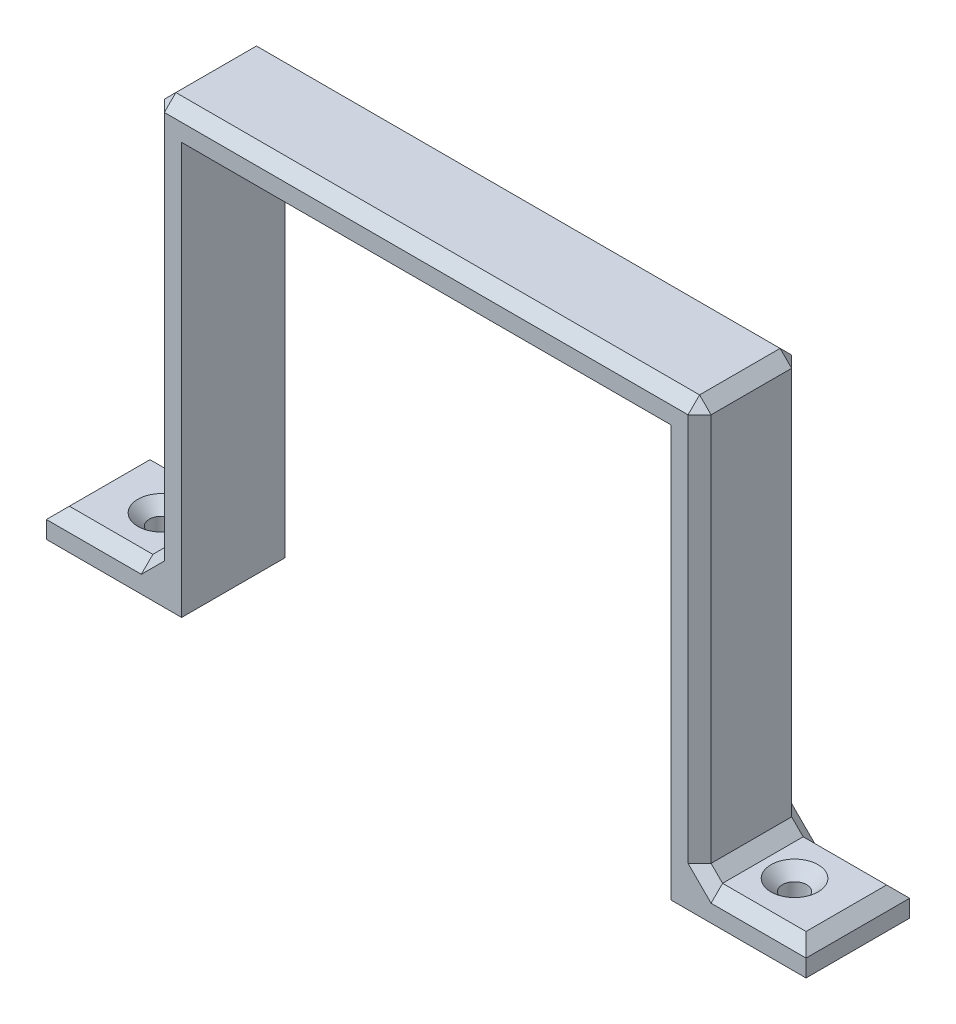
SolidWorks part; units mm, degrees
ref_plane "Front Plane" through (0, 0, 0) normal (0, 0, 1) x (1, 0, 0)
ref_plane "Top Plane" through (0, 0, 0) normal (0, 1, 0) x (1, 0, 0)
ref_plane "Right Plane" through (0, 0, 0) normal (1, 0, 0) x (0, 0, -1)
sketch "Sketch1" plane through (0, 0, 0) normal (0, 0, 1) x (1, 0, 0)
  line L0 (0, 48.7073) -> (0, -14.6895) construction
  line L1 (42.5, -27.85) -> (42.5, 43.65)
  line L2 (57, -27.85) -> (52, -27.85) construction
  line L3 (42.5, 43.65) -> (-42.5, 43.65)
  line L4 (-47.5, 48.65) -> (47.5, 48.65)
  line L5 (47.5, 48.65) -> (47.5, -22.85)
  line L6 (47.5, -22.85) -> (66, -22.85)
  line L7 (66, -22.85) -> (66, -27.85)
  line L8 (66, -27.85) -> (66, -43.45) construction
  line L9 (66, -27.85) -> (42.5, -27.85)
  line L10 (47.5, -22.85) -> (47.5, -27.85) construction
  line L11 (0, 48.65) -> (0, 43.65) construction
  line L12 (-47.5, -22.85) -> (-47.5, -27.85) construction
  line L13 (-66, -27.85) -> (-42.5, -27.85)
  line L14 (-66, -22.85) -> (-66, -27.85)
  line L15 (-47.5, -22.85) -> (-66, -22.85)
  line L16 (-47.5, 48.65) -> (-47.5, -22.85)
  line L17 (-42.5, -27.85) -> (-42.5, 43.65)
  dimension "D1" = 71.5
  dimension "D2" = 42.5
  dimension "D3" = 5
  dimension "D4" = 5
  dimension "D5" = 5
extrude "Boss-Extrude1" add sketch "Sketch1" along normal mid plane 18
sketch "Sketch2" plane through (0, -27.85, 0) normal (0, -1, 0) x (1, 0, 0)
  line L0 (0, 8.47) -> (0, -7.1138) construction
  circle A0 centre (55, 0) radius 2.1
  circle A1 centre (-55, 0) radius 2.1
  dimension "D1" = 4.2
extrude "Cut-Extrude1" cut sketch "Sketch2" against normal mid plane 18
chamfer "Chamfer1" distance 2 angle 45 2 edges at (-52.9, -22.85, 0) (55, -22.85, -2.1)
chamfer "Chamfer2" distance 2 angle 45 16 edges at (56.75, -22.85, 9) (56.75, -22.85, -9) (-56.75, -22.85, 9) (-66, -22.85, 0) (-56.75, -22.85, -9) (-47.5, 12.9, 9) (-47.5, -22.85, 0) (-47.5, 12.9, -9) (47.5, -22.85, 0) (47.5, 12.9, 9) (47.5, 12.9, -9) (47.5, 48.65, 0) (0, 48.65, 9) (-47.5, 48.65, 0) (0, 48.65, -9) (66, -22.85, 0)
